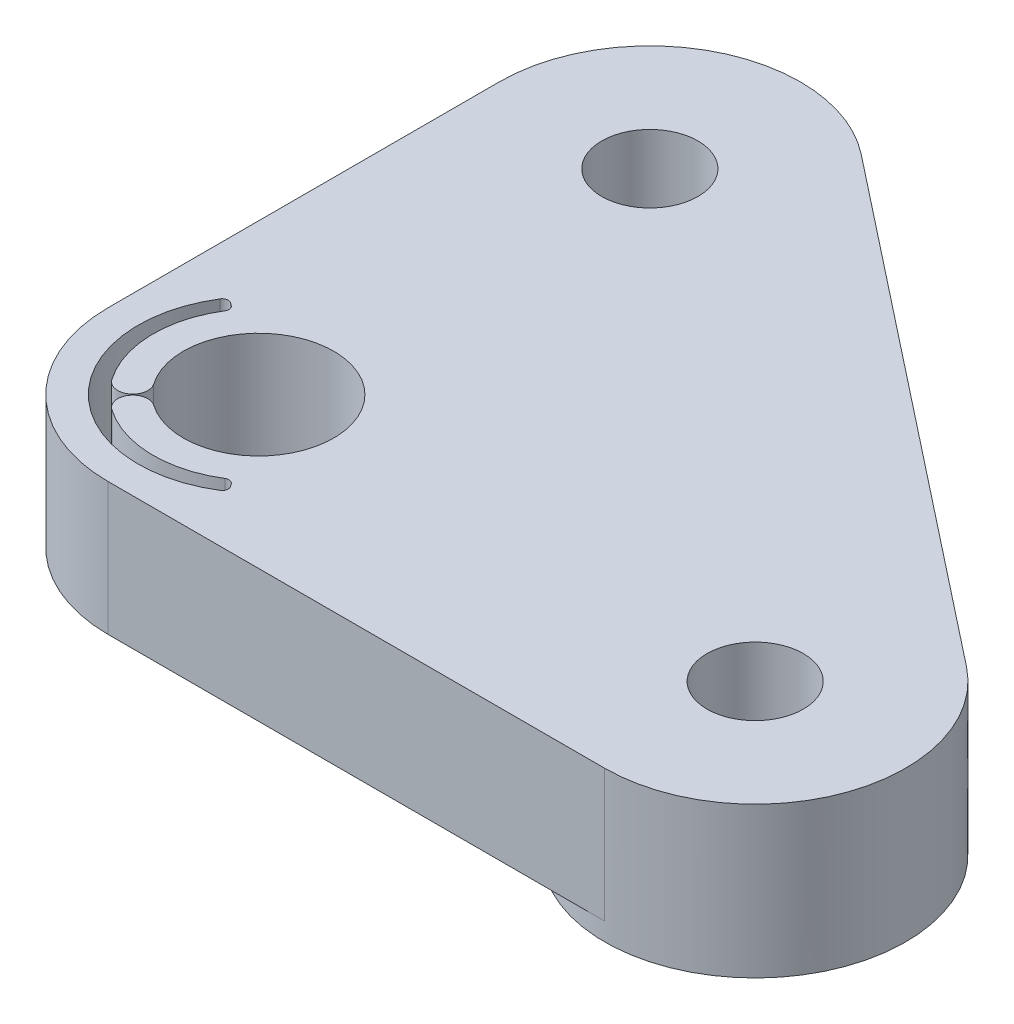
SolidWorks part; units mm, degrees
ref_plane "Front" through (0, 0, 0) normal (0, 0, 1) x (1, 0, 0)
ref_plane "Top" through (0, 0, 0) normal (0, 1, 0) x (1, 0, 0)
ref_plane "Right" through (0, 0, 0) normal (1, 0, 0) x (0, 0, -1)
sketch "Sketch1" plane through (0, 0, 0) normal (0, 1, 0) x (1, 0, 0)
  line L0 (0, 0) -> (16.5, 0) construction
  line L1 (16.5, 0) -> (0, 13) construction
  line L2 (0, 13) -> (0, 0) construction
  line L3 (-5, -5) -> (30.9254, -5)
  line L4 (30.9254, -5) -> (-5, 23.3048)
  line L5 (-5, 23.3048) -> (-5, -5)
  circle A0 centre (16.5, 0) radius 1.6
  circle A1 centre (0, 0) radius 2.5
  circle A2 centre (0, 13) radius 1.6
  dimension "D3" = 5
  dimension "D4" = 3.2
  dimension "D1" = 16.5
  dimension "D2" = 13
  dimension "D5" = 5
extrude "Boss-Extrude1" add sketch "Sketch1" along normal blind 1.57
fillet "Fillet1" radius 5 3 edges at (-5, 0.785, -23.3048) (-5, 0.785, 5) (30.9254, 0.785, 5)
other "Move Face1" [suppressed] offset 0.0762 parameters "D1"=0.0762
sketch "Sketch2" plane through (0, 1.57, 0) normal (0, 1, 0) x (1, 0, 0)
  line L3 (19.5944, 3.9275) -> (3.0944, 16.9275)
  line L4 (-5, 13) -> (-5, 0)
  line L5 (0, -5) -> (16.5, -5)
  line L6 (19.5944, 3.9275) -> (3.0944, 16.9275)
  line L7 (-5, 13) -> (-5, 0)
  line L8 (0, -5) -> (16.5, -5)
  circle A0 centre (0, 0) radius 2.5 construction
  circle A1 centre (16.5, 0) radius 1.6 construction
  circle A2 centre (0, 13) radius 1.6 construction
  arc A3 (3.0944, 16.9275) -> (-5, 13) centre (0, 13) ccw
  arc A4 (-5, 0) -> (0, -5) centre (0, 0) ccw
  arc A5 (16.5, -5) -> (19.5944, 3.9275) centre (16.5, 0) ccw
  arc A6 (3.0944, 16.9275) -> (-5, 13) centre (0, 13) ccw
  arc A7 (-5, 0) -> (0, -5) centre (0, 0) ccw
  arc A8 (16.5, -5) -> (19.5944, 3.9275) centre (16.5, 0) ccw
  circle A9 centre (0, 0) radius 2.5
  circle A10 centre (16.5, 0) radius 1.6
  circle A11 centre (0, 13) radius 1.6
  dimension "D1" = 0
extrude "Boss-Extrude2" add sketch "Sketch2" along normal blind 2.83
sketch "Sketch3" plane through (0, 0, 0) normal (0, -1, 0) x (1, 0, 0)
  circle A0 centre (16.5, 0) radius 5
  circle A1 centre (0, -13) radius 5
  circle A2 centre (0, -13) radius 1.6 construction
  circle A3 centre (16.5, 0) radius 1.6 construction
  circle A4 centre (0, -13) radius 1.6
  circle A5 centre (16.5, 0) radius 1.6
  arc A6 (19.5944, -3.9275) -> (16.5, 5) centre (16.5, 0) ccw construction
  arc A7 (-5, -13) -> (3.0944, -16.9275) centre (0, -13) ccw construction
extrude "Boss-Extrude3" add sketch "Sketch3" along normal blind 0.6
sketch "Sketch4" plane through (0, 4.4, 0) normal (0, 1, 0) x (1, 0, 0)
  line B0 (1.7207, -2.4575) -> (0, 0) construction
  line B1 (2.1191, -3.0264) -> (2.1766, -3.1085)
  line B2 (-3.0264, 2.1191) -> (-3.1085, 2.1766)
  line B3 (-1.7207, -2.4575) -> (0, 0) construction
  arc B4 (2.1187, -3.3928) -> (-3.3928, 2.1187) centre (0, 0) cw
  arc B5 (-1.4339, -2.0479) -> (-2.0075, -2.867) centre (-1.7207, -2.4575) ccw
  arc B6 (-2.0075, -2.867) -> (1.8496, -2.9714) centre (0, 0) ccw
  arc B7 (-2.867, -2.0075) -> (-2.9714, 1.8496) centre (0, 0) cw
  arc B8 (-2.0479, -1.4339) -> (-2.867, -2.0075) centre (-2.4575, -1.7207) cw
  arc B9 (-1.4339, -2.0479) -> (-2.0479, -1.4339) centre (0, 0) cw
  arc B10 (2.1191, -3.0264) -> (1.8496, -2.9714) centre (1.9553, -3.1411) ccw
  arc B11 (2.1766, -3.1085) -> (2.1187, -3.3928) centre (2.0127, -3.2232) cw
  arc B12 (-3.1085, 2.1766) -> (-3.3928, 2.1187) centre (-3.2232, 2.0127) ccw
  arc B13 (-3.0264, 2.1191) -> (-2.9714, 1.8496) centre (-3.1411, 1.9553) cw
sketch_block_instance "5mm_bore_flexure_relief-1"
sketch_block "5mm_bore_flexure_relief" parameters "D4"=2.5, "D6"=0.2, "D1"=80, "D2"=0.5, "D3"=70, "D5"=1
extrude "Cut-Extrude1" cut sketch "Sketch4" against normal blind 10
sketch "Sketch5" plane through (9.4139, 0, -11.9484) normal (0.6189, 0, -0.7855) x (-0.7855, 0, -0.6189)
  line L0 (-12.9606, 0.6) -> (8.0453, 0.6) construction
  line L1 (-12.9606, 4.4) -> (-12.9606, 0) construction
  line L2 (8.0453, 0) -> (8.0453, 4.4) construction
  line L3 (-12.9606, 0) -> (8.0453, 0) construction
  text T0 "LCR-01" font "Century Gothic" height in points 12
  dimension "D1" = 0.6
extrude "Part Num Left" cut sketch "Sketch5" against normal blind 0.4
mirror "Mirror1" [suppressed] of bodies 106 104
delete or keep bodies "Body-Delete/Keep 1" [suppressed] type keep bodies bodies 105
sketch "Sketch6" [suppressed] plane through (-13.2439, 0, -16.8096) normal (-0.6189, 0, -0.7855) x (-0.7855, 0, 0.6189)
  line L0 (-0.1904, 0.6) -> (20.8155, 0.6) construction
  line L1 (-0.1904, 0) -> (-0.1904, 4.4) construction
  line L2 (20.8155, 4.4) -> (20.8155, 0) construction
  line L3 (20.8155, 0) -> (-0.1904, 0) construction
  text T0 "RCR-01" font "Century Gothic" height in points 12
  dimension "D1" = 0.6
extrude "Part Num Right" [suppressed] cut sketch "Sketch6" against normal blind 0.4
